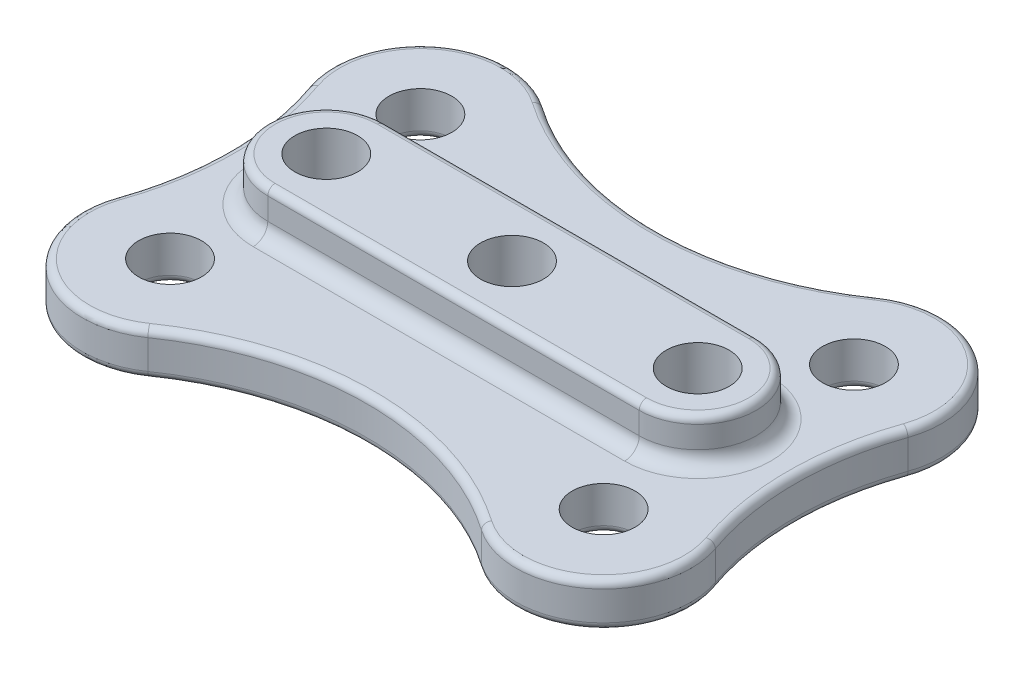
SolidWorks part; units mm, degrees
ref_plane "Front Plane" through (0, 0, 0) normal (0, 0, 1) x (1, 0, 0)
ref_plane "Top Plane" through (0, 0, 0) normal (0, 1, 0) x (1, 0, 0)
ref_plane "Right Plane" through (0, 0, 0) normal (1, 0, 0) x (0, 0, -1)
sketch "Sketch1" plane through (0, 0, 0) normal (0, 1, 0) x (1, 0, 0)
  line L0 (-11.2381, 13.3691) -> (2.391, 3.2067) construction
  line L1 (-20.8247, -14.559) -> (20.8247, -14.559) construction
  line L2 (-20.8247, -14.559) -> (-20.8247, 14.559) construction
  line L3 (-20.8247, 14.559) -> (20.8247, 14.559) construction
  line L4 (20.8247, -14.559) -> (20.8247, 14.559) construction
  line L5 (-20.8247, -14.559) -> (20.8247, 14.559) construction
  line L6 (-20.8247, 14.559) -> (20.8247, -14.559) construction
  line L7 (-2.391, 3.2067) -> (11.2381, 13.3691) construction
  line L8 (-20.1684, 5.8305) -> (-16.2625, -1.819) construction
  line L9 (-16.2625, 1.819) -> (-20.1684, -5.8305) construction
  line L10 (-11.2381, -13.3691) -> (2.391, -3.2067) construction
  line L11 (-2.391, -3.2067) -> (11.2381, -13.3691) construction
  line L12 (20.1684, -5.8305) -> (16.2625, 1.819) construction
  line L13 (16.2625, -1.819) -> (20.1684, 5.8305) construction
  line L14 (-11.2381, 13.3691) -> (0, 4.9895)
  line L15 (0, 4.9895) -> (11.2381, 13.3691)
  line L16 (20.1684, 5.8305) -> (17.1913, 0)
  line L17 (17.1913, 0) -> (20.1684, -5.8305)
  line L18 (11.2381, -13.3691) -> (0, -4.9895)
  line L19 (0, -4.9895) -> (-11.2381, -13.3691)
  line L20 (-20.1684, 5.8305) -> (-17.1913, 0)
  line L21 (-17.1913, 0) -> (-20.1684, -5.8305)
  circle A0 centre (0, 0) radius 17.1181 construction
  circle A2 centre (0, 0) radius 2.15
  circle A3 centre (14.8247, 8.559) radius 2.15
  circle A4 centre (14.8247, -8.559) radius 2.15
  circle A6 centre (-14.8247, -8.559) radius 2.15
  circle A7 centre (-14.8247, 8.559) radius 2.15
  circle A8 centre (12.7, 0) radius 2.15
  circle A9 centre (-12.7, 0) radius 2.15
  arc A10 (-11.2381, 13.3691) -> (-20.1684, 5.8305) centre (-14.8247, 8.559) ccw
  circle A11 centre (0, 0) radius 4 construction
  arc A12 (-20.1684, -5.8305) -> (-11.2381, -13.3691) centre (-14.8247, -8.559) ccw
  arc A13 (11.2381, -13.3691) -> (20.1684, -5.8305) centre (14.8247, -8.559) ccw
  arc A14 (20.1684, 5.8305) -> (11.2381, 13.3691) centre (14.8247, 8.559) ccw
  circle A15 centre (12.7, 0) radius 4 construction
  circle A16 centre (-12.7, 0) radius 4 construction
  point P43 (-17.1913, 0)
  point P44 (0, 4.9895)
  point P45 (17.1913, 0)
  point P46 (0, -4.9895)
  dimension "D1" = 34.2361
  dimension "D2" = 6
  dimension "D3" = 4.3
  dimension "D6" = 4.3
  dimension "D7" = 8
  dimension "D5" = 12.7
  dimension "D4" = 6
extrude "Boss-Extrude1" add sketch "Sketch1" along normal blind 3
fillet "Fillet1" radius 20 4 edges at (17.1913, 1.5, 0) (-17.1913, 1.5, 0) (0, 1.5, 4.9895) (0, 1.5, -4.9895)
sketch "Sketch2" plane through (0, 3, 0) normal (0, 1, 0) x (1, 0, 0)
  line L0 (-12.7, 0) -> (12.7, 0) construction
  line L1 (-12.7, 4) -> (12.7, 4)
  line L2 (-12.7, -4) -> (12.7, -4)
  arc A0 (-12.7, 4) -> (-12.7, -4) centre (-12.7, 0) ccw
  arc A1 (12.7, -4) -> (12.7, 4) centre (12.7, 0) ccw
  circle A2 centre (12.7, 0) radius 2.15 construction
  circle A3 centre (0, 0) radius 2.15 construction
  circle A4 centre (-12.7, 0) radius 2.15 construction
  circle A5 centre (12.7, 0) radius 2.15
  circle A6 centre (0, 0) radius 2.15
  circle A7 centre (-12.7, 0) radius 2.15
  arc A8 (-20.4903, -6.5839) -> (-20.4903, 6.5839) centre (-39.3755, 0) ccw
  arc A9 (-20.4903, -6.5839) -> (-11.4036, -13.4882) centre (-14.8247, -8.559) ccw
  arc A10 (11.4036, -13.4882) -> (-11.4036, -13.4882) centre (0, -29.9185) ccw
  arc A11 (11.4036, -13.4882) -> (20.4903, -6.5839) centre (14.8247, -8.559) ccw
  arc A12 (20.4903, 6.5839) -> (20.4903, -6.5839) centre (39.3755, 0) ccw
  arc A13 (20.4903, 6.5839) -> (11.4036, 13.4882) centre (14.8247, 8.559) ccw
  arc A14 (-11.4036, 13.4882) -> (11.4036, 13.4882) centre (0, 29.9185) ccw
  arc A15 (-11.4036, 13.4882) -> (-20.4903, 6.5839) centre (-14.8247, 8.559) ccw
  arc A16 (-20.4903, -6.5839) -> (-20.4903, 6.5839) centre (-39.3755, 0) ccw
  arc A17 (-20.4903, -6.5839) -> (-11.4036, -13.4882) centre (-14.8247, -8.559) ccw
  arc A18 (11.4036, -13.4882) -> (-11.4036, -13.4882) centre (0, -29.9185) ccw
  arc A19 (11.4036, -13.4882) -> (20.4903, -6.5839) centre (14.8247, -8.559) ccw
  arc A20 (20.4903, 6.5839) -> (20.4903, -6.5839) centre (39.3755, 0) ccw
  arc A21 (20.4903, 6.5839) -> (11.4036, 13.4882) centre (14.8247, 8.559) ccw
  arc A22 (-11.4036, 13.4882) -> (11.4036, 13.4882) centre (0, 29.9185) ccw
  arc A23 (-11.4036, 13.4882) -> (-20.4903, 6.5839) centre (-14.8247, 8.559) ccw
  point P12 (0, 0)
  circle M21 centre (12.7, 0) radius 2.15
  circle M38 centre (0, 0) radius 2.15
  circle M41 centre (-12.7, 0) radius 2.15
  dimension "D2" = 8
  dimension "D1" = 0
extrude "Boss-Extrude2" add sketch "Sketch2" along normal blind 3 contours L2 A1 L1 A0 A6 M41 M38 M21 region at (0, 3, -3.6566)
fillet "Fillet2" radius 0.5 27 edges at (-12.7, 0, 2.15) (-14.8247, 0, -6.409) (-14.8247, 0, 10.709) (14.8247, 0, 10.709) (14.8247, 0, -6.409) (12.7, 0, 2.15) (0, 0, 2.15) (-18.4547, 0, 13.3364) (0, 0, 9.9185) (18.4547, 0, 13.3364) (19.3755, 0, 0) (18.4547, 0, -13.3364) (0, 0, -9.9185) (-18.4547, 0, -13.3364) (-19.3755, 0, 0) (0, 3, -9.9185) (18.4547, 3, -13.3364) (19.3755, 3, 0) (18.4547, 3, 13.3364) (0, 3, 9.9185) (-18.4547, 3, 13.3364) (-19.3755, 3, 0) (-18.4547, 3, -13.3364) (-16.7, 6, 0) (0, 6, -4) (16.7, 6, 0) (0, 6, 4)
fillet "Fillet3" radius 1 4 edges at (-16.7, 3, 0) (0, 3, -4) (16.7, 3, 0) (0, 3, 4)
